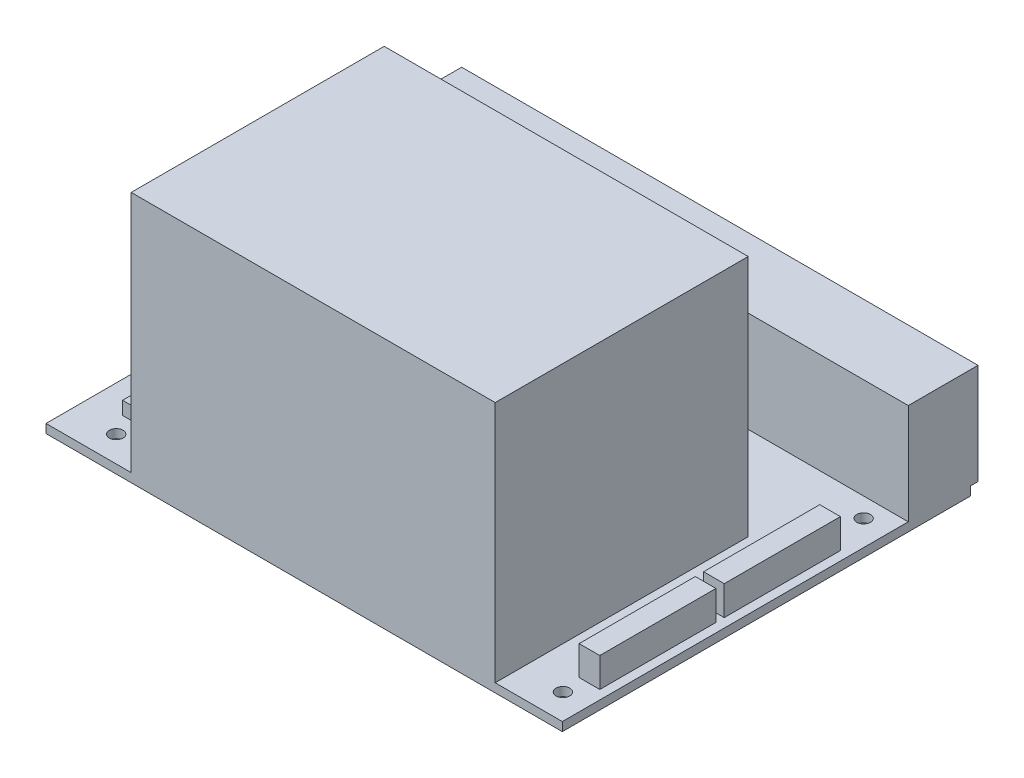
SolidWorks part; units mm, degrees
ref_plane "Front Plane" through (0, 0, 0) normal (0, 0, 1) x (1, 0, 0)
ref_plane "Top Plane" through (0, 0, 0) normal (0, 1, 0) x (1, 0, 0)
ref_plane "Right Plane" through (0, 0, 0) normal (1, 0, 0) x (0, 0, -1)
sketch "Sketch1" plane through (0, 0, 0) normal (0, 1, 0) x (1, 0, 0)
  line L0 (-41.4, 23.75) -> (-50, 23.75) construction
  line L1 (-50, 39.5) -> (50, 39.5)
  line L2 (-50, 39.5) -> (-50, -39.5)
  line L3 (-50, -39.5) -> (50, -39.5)
  line L4 (50, 39.5) -> (50, -39.5)
  line L5 (-41.4, 23.75) -> (-41.4, 39.5) construction
  line L6 (-41.4, -34.5) -> (-41.4, -39.5) construction
  line L7 (45.1, -34.5) -> (45.1, -39.5) construction
  line L8 (45.1, 23.75) -> (45.1, 39.5) construction
  line L9 (45.1, 23.75) -> (50, 23.75) construction
  line L10 (-41.4, 23.75) -> (-41.4, -34.5) construction
  line L11 (-41.4, 23.75) -> (45.1, 23.75) construction
  line L12 (45.1, 23.75) -> (45.1, -34.5) construction
  line L13 (45.1, -34.5) -> (-41.4, -34.5) construction
  circle A0 centre (-41.4, 23.75) radius 1.325
  circle A1 centre (-41.4, -34.5) radius 1.325
  circle A2 centre (45.1, 23.75) radius 1.325
  circle A3 centre (45.1, -34.5) radius 1.325
  point P4 (-50, 0)
  point P5 (0, 39.5)
  dimension "D3" = 2.65
  dimension "D1" = 79
  dimension "D2" = 100
  dimension "D4" = 15.75
  dimension "D5" = 8.6
  dimension "D6" = 86.5
  dimension "D7" = 58.25
extrude "Boss-Extrude1" add sketch "Sketch1" along normal blind 1.7
sketch "Sketch2" plane through (0, 0, -39.5) normal (0, 0, -1) x (-1, 0, 0)
  line L1 (-50, 1.7) -> (50, 1.7)
  line L2 (-50, 1.7) -> (-50, 21.2)
  line L3 (-50, 21.2) -> (50, 21.2)
  line L4 (50, 1.7) -> (50, 21.2)
  dimension "D1" = 19.5
extrude "Boss-Extrude2" add sketch "Sketch2" along normal blind 1.5 separate body
extrude "Boss-Extrude3" add sketch "Sketch2<2>" against normal blind 12
sketch "Sketch2<2>" plane through (0, 0, -39.5) normal (0, 0, -1) x (-1, 0, 0) same geometry as "Sketch2"
sketch "Sketch3" plane through (0, 1.7, 0) normal (0, 1, 0) x (1, 0, 0)
  line L0 (-50, -39.5) -> (50, -39.5) construction
  line L1 (-33.5, 9.5) -> (37, 9.5)
  line L2 (-33.5, 9.5) -> (-33.5, -39.5)
  line L3 (-33.5, -39.5) -> (37, -39.5)
  line L4 (37, 9.5) -> (37, -39.5)
  line L5 (-50, 27.5) -> (-50, -39.5) construction
  dimension "D1" = 49
  dimension "D2" = 16.5
  dimension "D3" = 13
extrude "Boss-Extrude4" add sketch "Sketch3" along normal blind 47
sketch "Sketch4" plane through (0, 1.7, 0) normal (0, 1, 0) x (1, 0, 0)
  line L0 (-41.4, 25.075) -> (-41.4, 22.425) construction
  line L1 (-43.925, 20) -> (-38.875, 20)
  line L2 (-43.925, 20) -> (-43.925, -30.75)
  line L3 (-43.925, -30.75) -> (-38.875, -30.75)
  line L4 (-38.875, 20) -> (-38.875, -30.75)
  line L5 (-42.725, 23.75) -> (-40.075, 23.75) construction
  line L6 (-41.4, -30.75) -> (-41.4, -33.175) construction
  line L7 (-42.725, -34.5) -> (-40.075, -34.5) construction
  line L8 (-41.4, -33.175) -> (-41.4, -35.825) construction
  line L9 (-41.4, 22.425) -> (-41.4, 20) construction
  circle A0 centre (-41.4, 23.75) radius 1.325 construction
  circle A1 centre (-41.4, -34.5) radius 1.325 construction
  point P8 (-41.4, 20)
  dimension "D1" = 50.75
  dimension "D2" = 5.05
extrude "Boss-Extrude5" add sketch "Sketch4" along normal blind 2.55
sketch "Sketch5" plane through (0, 4.25, 0) normal (0, 1, 0) x (1, 0, 0)
  line L0 (-40.4822, 19.0972) -> (-39.8422, 19.0972)
  line L1 (-43.0222, 19.0972) -> (-42.3822, 19.0972)
  line L2 (-43.0222, 19.0972) -> (-43.0222, 18.4572)
  line L3 (-43.0222, 18.4572) -> (-42.3822, 18.4572)
  line L4 (-42.3822, 19.0972) -> (-42.3822, 18.4572)
  line L5 (-40.4822, 19.0972) -> (-40.4822, 18.4572)
  line L6 (-40.4822, 18.4572) -> (-39.8422, 18.4572)
  line L7 (-39.8422, 19.0972) -> (-39.8422, 18.4572)
  line L8 (-43.925, 18.7772) -> (-43.0222, 18.7772) construction
  line L9 (-43.925, 20) -> (-43.925, -30.75) construction
  line L10 (-39.8422, 18.7772) -> (-38.9395, 18.7772) construction
  line L13 (-42.7022, 19.0972) -> (-42.7022, 20) construction
  line L14 (-38.875, 20) -> (-43.925, 20) construction
  line L15 (-43.0222, 16.5572) -> (-43.0222, 15.9172)
  line L16 (-43.0222, 16.5572) -> (-42.3822, 16.5572)
  line L17 (-42.3822, 16.5572) -> (-42.3822, 15.9172)
  line L18 (-43.0222, 15.9172) -> (-42.3822, 15.9172)
  line L19 (-40.4822, 16.5572) -> (-40.4822, 15.9172)
  line L20 (-40.4822, 16.5572) -> (-39.8422, 16.5572)
  line L21 (-40.4822, 15.9172) -> (-39.8422, 15.9172)
  line L22 (-39.8422, 16.5572) -> (-39.8422, 15.9172)
  line L23 (-43.0222, 14.0172) -> (-43.0222, 13.3772)
  line L24 (-43.0222, 14.0172) -> (-42.3822, 14.0172)
  line L25 (-42.3822, 14.0172) -> (-42.3822, 13.3772)
  line L26 (-43.0222, 13.3772) -> (-42.3822, 13.3772)
  line L27 (-40.4822, 14.0172) -> (-40.4822, 13.3772)
  line L28 (-40.4822, 14.0172) -> (-39.8422, 14.0172)
  line L29 (-40.4822, 13.3772) -> (-39.8422, 13.3772)
  line L30 (-39.8422, 14.0172) -> (-39.8422, 13.3772)
  line L31 (-43.0222, 11.4772) -> (-43.0222, 10.8372)
  line L32 (-43.0222, 11.4772) -> (-42.3822, 11.4772)
  line L33 (-42.3822, 11.4772) -> (-42.3822, 10.8372)
  line L34 (-43.0222, 10.8372) -> (-42.3822, 10.8372)
  line L35 (-40.4822, 11.4772) -> (-40.4822, 10.8372)
  line L36 (-40.4822, 11.4772) -> (-39.8422, 11.4772)
  line L37 (-40.4822, 10.8372) -> (-39.8422, 10.8372)
  line L38 (-39.8422, 11.4772) -> (-39.8422, 10.8372)
  line L39 (-43.0222, 8.9372) -> (-43.0222, 8.2972)
  line L40 (-43.0222, 8.9372) -> (-42.3822, 8.9372)
  line L41 (-42.3822, 8.9372) -> (-42.3822, 8.2972)
  line L42 (-43.0222, 8.2972) -> (-42.3822, 8.2972)
  line L43 (-40.4822, 8.9372) -> (-40.4822, 8.2972)
  line L44 (-40.4822, 8.9372) -> (-39.8422, 8.9372)
  line L45 (-40.4822, 8.2972) -> (-39.8422, 8.2972)
  line L46 (-39.8422, 8.9372) -> (-39.8422, 8.2972)
  line L47 (-43.0222, 6.3972) -> (-43.0222, 5.7572)
  line L48 (-43.0222, 6.3972) -> (-42.3822, 6.3972)
  line L49 (-42.3822, 6.3972) -> (-42.3822, 5.7572)
  line L50 (-43.0222, 5.7572) -> (-42.3822, 5.7572)
  line L51 (-40.4822, 6.3972) -> (-40.4822, 5.7572)
  line L52 (-40.4822, 6.3972) -> (-39.8422, 6.3972)
  line L53 (-40.4822, 5.7572) -> (-39.8422, 5.7572)
  line L54 (-39.8422, 6.3972) -> (-39.8422, 5.7572)
  line L55 (-43.0222, 3.8572) -> (-43.0222, 3.2172)
  line L56 (-43.0222, 3.8572) -> (-42.3822, 3.8572)
  line L57 (-42.3822, 3.8572) -> (-42.3822, 3.2172)
  line L58 (-43.0222, 3.2172) -> (-42.3822, 3.2172)
  line L59 (-40.4822, 3.8572) -> (-40.4822, 3.2172)
  line L60 (-40.4822, 3.8572) -> (-39.8422, 3.8572)
  line L61 (-40.4822, 3.2172) -> (-39.8422, 3.2172)
  line L62 (-39.8422, 3.8572) -> (-39.8422, 3.2172)
  line L63 (-43.0222, 1.3172) -> (-43.0222, 0.6772)
  line L64 (-43.0222, 1.3172) -> (-42.3822, 1.3172)
  line L65 (-42.3822, 1.3172) -> (-42.3822, 0.6772)
  line L66 (-43.0222, 0.6772) -> (-42.3822, 0.6772)
  line L67 (-40.4822, 1.3172) -> (-40.4822, 0.6772)
  line L68 (-40.4822, 1.3172) -> (-39.8422, 1.3172)
  line L69 (-40.4822, 0.6772) -> (-39.8422, 0.6772)
  line L70 (-39.8422, 1.3172) -> (-39.8422, 0.6772)
  line L71 (-43.0222, -1.2228) -> (-43.0222, -1.8628)
  line L72 (-43.0222, -1.2228) -> (-42.3822, -1.2228)
  line L73 (-42.3822, -1.2228) -> (-42.3822, -1.8628)
  line L74 (-43.0222, -1.8628) -> (-42.3822, -1.8628)
  line L75 (-40.4822, -1.2228) -> (-40.4822, -1.8628)
  line L76 (-40.4822, -1.2228) -> (-39.8422, -1.2228)
  line L77 (-40.4822, -1.8628) -> (-39.8422, -1.8628)
  line L78 (-39.8422, -1.2228) -> (-39.8422, -1.8628)
  line L79 (-43.0222, -3.7628) -> (-43.0222, -4.4028)
  line L80 (-43.0222, -3.7628) -> (-42.3822, -3.7628)
  line L81 (-42.3822, -3.7628) -> (-42.3822, -4.4028)
  line L82 (-43.0222, -4.4028) -> (-42.3822, -4.4028)
  line L83 (-40.4822, -3.7628) -> (-40.4822, -4.4028)
  line L84 (-40.4822, -3.7628) -> (-39.8422, -3.7628)
  line L85 (-40.4822, -4.4028) -> (-39.8422, -4.4028)
  line L86 (-39.8422, -3.7628) -> (-39.8422, -4.4028)
  line L87 (-43.0222, -6.3028) -> (-43.0222, -6.9428)
  line L88 (-43.0222, -6.3028) -> (-42.3822, -6.3028)
  line L89 (-42.3822, -6.3028) -> (-42.3822, -6.9428)
  line L90 (-43.0222, -6.9428) -> (-42.3822, -6.9428)
  line L91 (-40.4822, -6.3028) -> (-40.4822, -6.9428)
  line L92 (-40.4822, -6.3028) -> (-39.8422, -6.3028)
  line L93 (-40.4822, -6.9428) -> (-39.8422, -6.9428)
  line L94 (-39.8422, -6.3028) -> (-39.8422, -6.9428)
  line L95 (-43.0222, -8.8428) -> (-43.0222, -9.4828)
  line L96 (-43.0222, -8.8428) -> (-42.3822, -8.8428)
  line L97 (-42.3822, -8.8428) -> (-42.3822, -9.4828)
  line L98 (-43.0222, -9.4828) -> (-42.3822, -9.4828)
  line L99 (-40.4822, -8.8428) -> (-40.4822, -9.4828)
  line L100 (-40.4822, -8.8428) -> (-39.8422, -8.8428)
  line L101 (-40.4822, -9.4828) -> (-39.8422, -9.4828)
  line L102 (-39.8422, -8.8428) -> (-39.8422, -9.4828)
  line L103 (-43.0222, -11.3828) -> (-43.0222, -12.0228)
  line L104 (-43.0222, -11.3828) -> (-42.3822, -11.3828)
  line L105 (-42.3822, -11.3828) -> (-42.3822, -12.0228)
  line L106 (-43.0222, -12.0228) -> (-42.3822, -12.0228)
  line L107 (-40.4822, -11.3828) -> (-40.4822, -12.0228)
  line L108 (-40.4822, -11.3828) -> (-39.8422, -11.3828)
  line L109 (-40.4822, -12.0228) -> (-39.8422, -12.0228)
  line L110 (-39.8422, -11.3828) -> (-39.8422, -12.0228)
  line L111 (-43.0222, -13.9228) -> (-43.0222, -14.5628)
  line L112 (-43.0222, -13.9228) -> (-42.3822, -13.9228)
  line L113 (-42.3822, -13.9228) -> (-42.3822, -14.5628)
  line L114 (-43.0222, -14.5628) -> (-42.3822, -14.5628)
  line L115 (-40.4822, -13.9228) -> (-40.4822, -14.5628)
  line L116 (-40.4822, -13.9228) -> (-39.8422, -13.9228)
  line L117 (-40.4822, -14.5628) -> (-39.8422, -14.5628)
  line L118 (-39.8422, -13.9228) -> (-39.8422, -14.5628)
  line L119 (-43.0222, -16.4628) -> (-43.0222, -17.1028)
  line L120 (-43.0222, -16.4628) -> (-42.3822, -16.4628)
  line L121 (-42.3822, -16.4628) -> (-42.3822, -17.1028)
  line L122 (-43.0222, -17.1028) -> (-42.3822, -17.1028)
  line L123 (-40.4822, -16.4628) -> (-40.4822, -17.1028)
  line L124 (-40.4822, -16.4628) -> (-39.8422, -16.4628)
  line L125 (-40.4822, -17.1028) -> (-39.8422, -17.1028)
  line L126 (-39.8422, -16.4628) -> (-39.8422, -17.1028)
  line L127 (-43.0222, -19.0028) -> (-43.0222, -19.6428)
  line L128 (-43.0222, -19.0028) -> (-42.3822, -19.0028)
  line L129 (-42.3822, -19.0028) -> (-42.3822, -19.6428)
  line L130 (-43.0222, -19.6428) -> (-42.3822, -19.6428)
  line L131 (-40.4822, -19.0028) -> (-40.4822, -19.6428)
  line L132 (-40.4822, -19.0028) -> (-39.8422, -19.0028)
  line L133 (-40.4822, -19.6428) -> (-39.8422, -19.6428)
  line L134 (-39.8422, -19.0028) -> (-39.8422, -19.6428)
  line L135 (-43.0222, -21.5428) -> (-43.0222, -22.1828)
  line L136 (-43.0222, -21.5428) -> (-42.3822, -21.5428)
  line L137 (-42.3822, -21.5428) -> (-42.3822, -22.1828)
  line L138 (-43.0222, -22.1828) -> (-42.3822, -22.1828)
  line L139 (-40.4822, -21.5428) -> (-40.4822, -22.1828)
  line L140 (-40.4822, -21.5428) -> (-39.8422, -21.5428)
  line L141 (-40.4822, -22.1828) -> (-39.8422, -22.1828)
  line L142 (-39.8422, -21.5428) -> (-39.8422, -22.1828)
  line L143 (-43.0222, -24.0828) -> (-43.0222, -24.7228)
  line L144 (-43.0222, -24.0828) -> (-42.3822, -24.0828)
  line L145 (-42.3822, -24.0828) -> (-42.3822, -24.7228)
  line L146 (-43.0222, -24.7228) -> (-42.3822, -24.7228)
  line L147 (-40.4822, -24.0828) -> (-40.4822, -24.7228)
  line L148 (-40.4822, -24.0828) -> (-39.8422, -24.0828)
  line L149 (-40.4822, -24.7228) -> (-39.8422, -24.7228)
  line L150 (-39.8422, -24.0828) -> (-39.8422, -24.7228)
  line L151 (-43.0222, -26.6228) -> (-43.0222, -27.2628)
  line L152 (-43.0222, -26.6228) -> (-42.3822, -26.6228)
  line L153 (-42.3822, -26.6228) -> (-42.3822, -27.2628)
  line L154 (-43.0222, -27.2628) -> (-42.3822, -27.2628)
  line L155 (-40.4822, -26.6228) -> (-40.4822, -27.2628)
  line L156 (-40.4822, -26.6228) -> (-39.8422, -26.6228)
  line L157 (-40.4822, -27.2628) -> (-39.8422, -27.2628)
  line L158 (-39.8422, -26.6228) -> (-39.8422, -27.2628)
  line L159 (-43.0222, -29.1628) -> (-43.0222, -29.8028)
  line L160 (-43.0222, -29.1628) -> (-42.3822, -29.1628)
  line L161 (-42.3822, -29.1628) -> (-42.3822, -29.8028)
  line L162 (-43.0222, -29.8028) -> (-42.3822, -29.8028)
  line L163 (-40.4822, -29.1628) -> (-40.4822, -29.8028)
  line L164 (-40.4822, -29.1628) -> (-39.8422, -29.1628)
  line L165 (-40.4822, -29.8028) -> (-39.8422, -29.8028)
  line L166 (-39.8422, -29.1628) -> (-39.8422, -29.8028)
  point P8 (-42.7022, 19.0972)
  point P9 (-40.1622, 19.0972)
  dimension "D1" = 0.64
  dimension "D2" = 0.64
  dimension "D3" = 2.54
  dimension "D4" = 20
extrude "Boss-Extrude6" add sketch "Sketch5" along normal blind 4.5
sketch "Sketch6" plane through (0, 1.7, 0) normal (0, 1, 0) x (1, 0, 0)
  line L0 (44.25, 16.1) -> (48.25, 16.1)
  line L1 (44.25, -8) -> (48.25, -8)
  line L2 (44.25, -8) -> (44.25, -30.5)
  line L3 (44.25, -30.5) -> (48.25, -30.5)
  line L4 (48.25, -8) -> (48.25, -30.5)
  line L5 (44.25, 16.1) -> (44.25, -6.4)
  line L6 (44.25, -6.4) -> (48.25, -6.4)
  line L7 (48.25, 16.1) -> (48.25, -6.4)
  dimension "D1" = 1.75
  dimension "D2" = 4
  dimension "D3" = 9
  dimension "D4" = 22.5
  dimension "D5" = 1.6
extrude "Boss-Extrude7" add sketch "Sketch6" along normal blind 5.7
